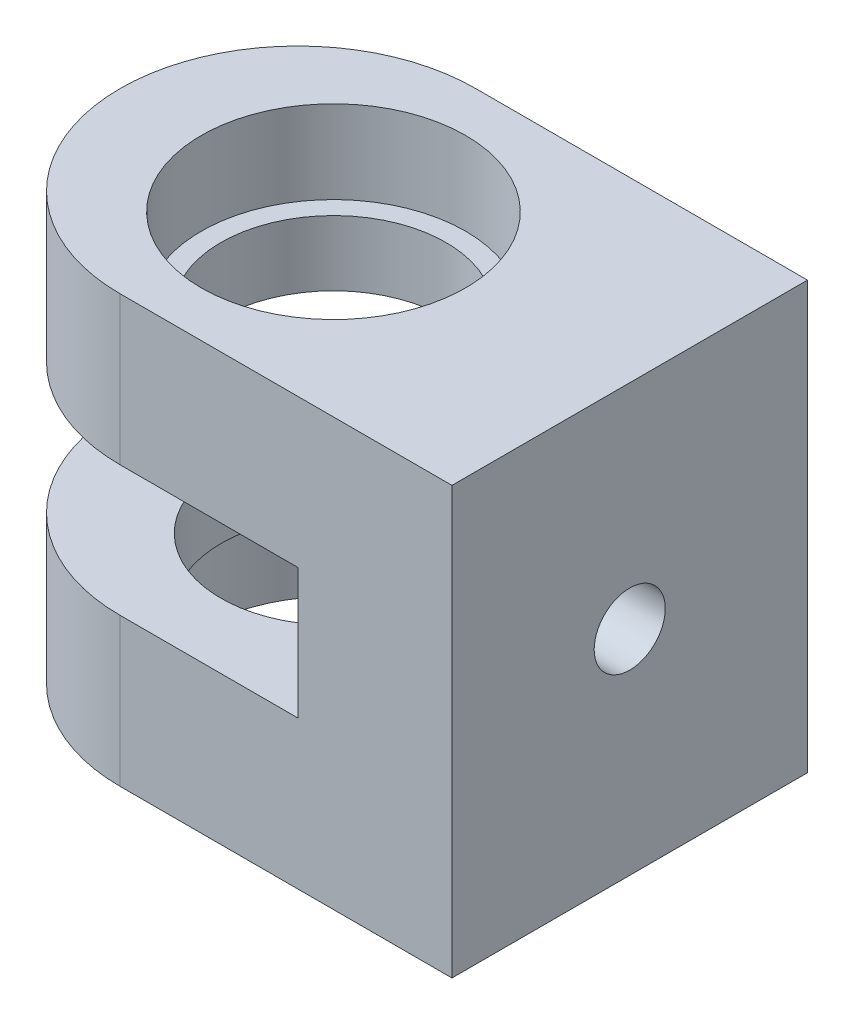
SolidWorks part; units mm, degrees
ref_plane "Спереди" through (0, 0, 0) normal (0, 0, 1) x (1, 0, 0)
ref_plane "Сверху" through (0, 0, 0) normal (0, 1, 0) x (1, 0, 0)
ref_plane "Справа" through (0, 0, 0) normal (1, 0, 0) x (0, 0, -1)
sketch "Sketch1" plane through (0, 0, 0) normal (0, 1, 0) x (1, 0, 0)
  line L1 (21.5, -15) -> (-21.5, -15)
  line L2 (21.5, -15) -> (21.5, 15)
  line L3 (21.5, 15) -> (-21.5, 15)
  line L4 (-21.5, -15) -> (-21.5, 15)
  line L5 (21.5, -15) -> (-21.5, 15) construction
  line L6 (21.5, 15) -> (-21.5, -15) construction
  point P0 (0, 0)
  dimension "D1" = 43
  dimension "D2" = 30
extrude "Boss-Extrude1" add sketch "Sketch1" along normal blind 36
sketch "Sketch2" plane through (-21.5, 0, 0) normal (-1, 0, 0) x (0, 0, 1)
  line L0 (0, 36) -> (0, 0) construction
  line L1 (-15, 36) -> (15, 36) construction
  line L2 (-15, 0) -> (15, 0) construction
  line L3 (-15, 36) -> (-15, 0) construction
  line L4 (15, 12.5) -> (-15, 12.5)
  line L5 (15, 12.5) -> (15, 23.5)
  line L6 (15, 23.5) -> (-15, 23.5)
  line L7 (-15, 12.5) -> (-15, 23.5)
  line L8 (15, 12.5) -> (-15, 23.5) construction
  line L9 (15, 23.5) -> (-15, 12.5) construction
  point P6 (0, 18)
  dimension "D1" = 11
extrude "Cut-Extrude1" cut sketch "Sketch2" against normal blind 30
sketch "Sketch3" plane through (0, 36, 0) normal (0, 1, 0) x (1, 0, 0)
  line L0 (-21.5, 0) -> (21.5, 0) construction
  line L1 (-21.5, 15) -> (-21.5, -15) construction
  line L2 (21.5, -15) -> (21.5, 15) construction
  circle A0 centre (-3.5, 0) radius 11.15
  dimension "D1" = 22.3
  dimension "D2" = 18
extrude "Cut-Extrude2" cut sketch "Sketch3" against normal blind 7
sketch "Sketch4" plane through (0, 0, 0) normal (0, -1, 0) x (1, 0, 0)
  line L0 (-21.5, 0) -> (21.5, 0) construction
  line L1 (-21.5, -15) -> (-21.5, 15) construction
  line L2 (21.5, 15) -> (21.5, -15) construction
  circle A0 centre (-3.5, 0) radius 11.15
  dimension "D1" = 22.3
  dimension "D2" = 18
extrude "Cut-Extrude3" cut sketch "Sketch4" against normal blind 7
sketch "Sketch5" plane through (0, 29, 0) normal (0, 1, 0) x (1, 0, 0)
  circle A0 centre (-3.5, 0) radius 9.5
  dimension "D1" = 19
extrude "Cut-Extrude4" cut sketch "Sketch5" against normal through all
sketch "Sketch6" plane through (8.5, 0, 0) normal (-1, 0, 0) x (0, 0, 1)
  line L0 (-15, 18) -> (15, 18) construction
  line L1 (-15, 23.5) -> (-15, 12.5) construction
  line L2 (15, 12.5) -> (15, 23.5) construction
  line L3 (-15, 12.5) -> (15, 12.5) construction
  line L4 (-3, 23.1962) -> (-6, 18)
  line L5 (-6, 18) -> (-3, 12.8038)
  line L6 (-3, 12.8038) -> (3, 12.8038)
  line L7 (3, 12.8038) -> (6, 18)
  line L8 (6, 18) -> (3, 23.1962)
  line L9 (3, 23.1962) -> (-3, 23.1962)
  circle A0 centre (0, 18) radius 6 construction
  dimension "D1" = 12
extrude "Cut-Extrude5" cut sketch "Sketch6" against normal blind 5
sketch "Sketch7" plane through (13.5, 0, 0) normal (-1, 0, 0) x (0, 0, 1)
  line L0 (6, 18) -> (-6, 18) construction
  circle A0 centre (0, 18) radius 3
  dimension "D1" = 6
extrude "Cut-Extrude6" cut sketch "Sketch7" against normal through all
fillet "Fillet2" radius 15 4 edges at (-21.5, 6.25, -15) (-21.5, 6.25, 15) (-21.5, 29.75, 15) (-21.5, 29.75, -15)
